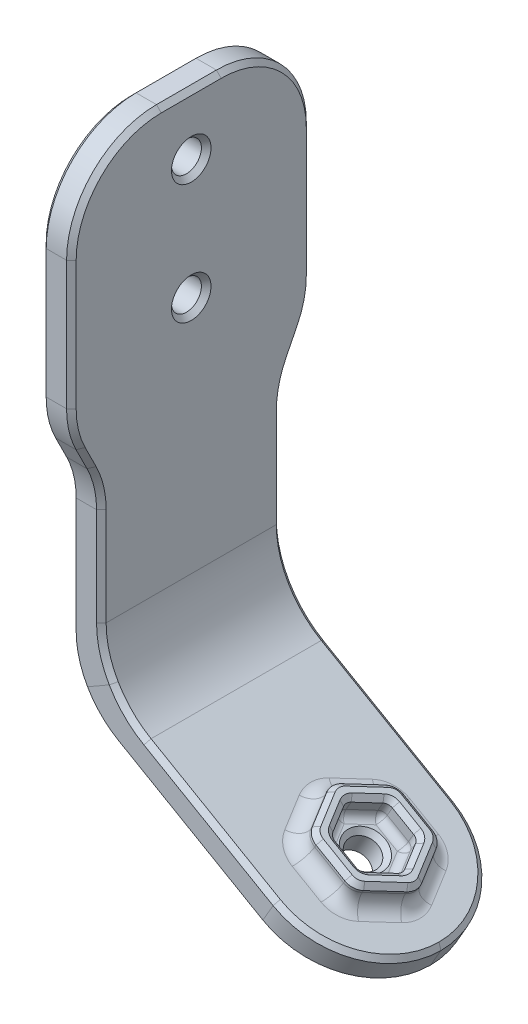
SolidWorks part; units mm, degrees
material "Onyx"
ref_plane "Front Plane" through (0, 0, 0) normal (0, 0, 1) x (1, 0, 0)
ref_plane "Top Plane" through (0, 0, 0) normal (0, 1, 0) x (1, 0, 0)
ref_plane "Right Plane" through (0, 0, 0) normal (1, 0, 0) x (0, 0, -1)
sketch "Sketch1" plane through (0, 0, 0) normal (0, 0, 1) x (1, 0, 0)
  line L0 (0, 0) -> (0, -31.75)
  line L1 (0, -31.75) -> (0, -50.8)
  line L2 (0, -50.8) -> (27.4963, -66.675)
  dimension "D2" = 19.05
  dimension "D1" = 31.75
  dimension "D3" = 180
  dimension "D4" = 120
  dimension "D5" = 31.75
sketch "Sketch2" plane through (0, 0, 0) normal (0, 1, 0) x (1, 0, 0)
  line L1 (-1.5875, -9.525) -> (1.5875, -9.525)
  line L2 (-1.5875, -9.525) -> (-1.5875, 9.525)
  line L3 (-1.5875, 9.525) -> (1.5875, 9.525)
  line L4 (1.5875, -9.525) -> (1.5875, 9.525)
  line L5 (-1.5875, -9.525) -> (1.5875, 9.525) construction
  line L6 (-1.5875, 9.525) -> (1.5875, -9.525) construction
  point P0 (0, 0)
  dimension "D1" = 3.175
  dimension "D2" = 19.05
sweep "Sweep1" add profiles "Sketch2" path "Sketch1"
sketch "Sketch4" plane through (-1.5875, 0, 0) normal (-1, 0, 0) x (0, 0, 1)
  line L0 (-12.7, -25.4) -> (-9.525, -31.75)
  line L1 (-12.7, 0) -> (12.7, 0)
  line L2 (-12.7, 0) -> (-12.7, -25.4)
  line L3 (-12.7, -25.4) -> (12.7, -25.4) construction
  line L4 (12.7, 0) -> (12.7, -25.4)
  line L5 (-9.525, 0) -> (-9.525, -31.75) construction
  line L6 (-9.525, -31.75) -> (9.525, -31.75)
  line L7 (9.525, 0) -> (9.525, -31.75) construction
  line L8 (9.525, -31.75) -> (12.7, -25.4)
  point P4 (0, 0)
  dimension "D1" = 25.4
  dimension "D2" = 6.35
  dimension "D3" = 25.4
extrude "Boss-Extrude1" add sketch "Sketch4" against normal up to surface (3.175 mm away) up to face at (1.5875, -15.875, 0)
sketch "Sketch3" plane through (-1.5875, 0, 0) normal (-1, 0, 0) x (0, 0, 1)
  line L0 (0, -19.05) -> (0, -6.35) construction
  line L1 (0, -6.35) -> (0, 0) construction
  circle A0 centre (0, -6.35) radius 1.5875
  circle A1 centre (0, -19.05) radius 1.5875
  dimension "D1" = 3.175
  dimension "D2" = 6.35
  dimension "D3" = 12.7
extrude "Cut-Extrude1" cut sketch "Sketch3" against normal up to next
sketch "Sketch5" plane through (-21.2033, -36.7252, 0) normal (0.5, 0.866, 0) x (0.866, -0.5, 0)
  line L0 (47.625, 0) -> (57.15, 0) construction
  line L1 (57.15, -9.525) -> (57.15, 9.525) construction
  circle A0 centre (47.625, 0) radius 1.5875
  dimension "D1" = 3.175
  dimension "D2" = 9.525
extrude "Cut-Extrude2" cut sketch "Sketch5" against normal up to next
sketch "Sketch6" plane through (-21.2033, -36.7252, 0) normal (0.5, 0.866, 0) x (0.866, -0.5, 0)
  line L1 (49.3848, 3.048) -> (45.8652, 3.048)
  line L2 (45.8652, 3.048) -> (44.1055, 0)
  line L3 (44.1055, 0) -> (45.8652, -3.048)
  line L4 (45.8652, -3.048) -> (49.3848, -3.048)
  line L5 (49.3848, -3.048) -> (51.1445, 0)
  line L6 (51.1445, 0) -> (49.3848, 3.048)
  line L7 (50.3013, 4.6355) -> (44.9487, 4.6355)
  line L8 (44.9487, 4.6355) -> (42.2724, 0)
  line L9 (42.2724, 0) -> (44.9487, -4.6355)
  line L10 (44.9487, -4.6355) -> (50.3013, -4.6355)
  line L11 (50.3013, -4.6355) -> (52.9776, 0)
  line L12 (52.9776, 0) -> (50.3013, 4.6355)
  circle A0 centre (47.625, 0) radius 3.048 construction
  circle A1 centre (47.625, 0) radius 4.6355 construction
  dimension "D1" = 6.096
  dimension "D2" = 1.5875
extrude "Boss-Extrude2" add sketch "Sketch6" along normal blind 2.3813
fillet "Fillet1" radius 9.525 2 edges at (27.4963, -66.675, -9.525) (27.4963, -66.675, 9.525)
fillet "Fillet2" radius 9.525 2 edges at (-1.5875, -51.7165, 0) (1.5875, -49.8835, 0)
fillet "Fillet3" radius 9.525 6 edges at (0, 0, -12.7) (0, 0, 12.7) (0, -25.4, -12.7) (0, -31.75, -9.525) (0, -25.4, 12.7) (0, -31.75, 9.525)
fillet "Fillet4" radius 1.5875 12 edges at (25.272, -62.1829, 0) (16.001, -56.8303, 0) (18.3187, -58.1684, -4.6355) (22.9542, -60.8447, -4.6355) (18.3187, -58.1684, 4.6355) (22.9542, -60.8447, 4.6355) (20.0412, -60.5377, -4.6355) (16.5645, -58.5305, -2.3177) (16.5645, -58.5305, 2.3178) (20.0412, -60.5377, 4.6355) (23.5178, -62.5449, -2.3178) (23.5178, -62.5449, 2.3177)
fillet "Fillet5" radius 0.7937 12 edges at (20.0412, -60.5377, 3.048) (17.7552, -59.2179, 1.524) (20.0412, -60.5377, -3.048) (22.3272, -61.8575, -1.524) (22.3272, -61.8575, 1.524) (17.7552, -59.2179, -1.524) (17.5885, -57.7468, 0) (19.1125, -58.6267, 3.048) (22.1605, -60.3865, 3.048) (23.6845, -61.2663, 0) (22.1605, -60.3865, -3.048) (19.1125, -58.6267, -3.048)
chamfer "Chamfer1" distance 0.508 angle 45 72 edges at (19.761, -57.6263, -2.9417) (18.9458, -57.1556, -1.524) (18.2901, -56.7771, 0) (18.9458, -57.1556, 1.524) (19.761, -57.6263, 2.9417) (21.2318, -58.4755, 3.048) (22.7026, -59.3246, 2.9417) (23.5178, -59.7953, 1.524) (24.1734, -60.1738, 0) (23.5178, -59.7953, -1.524) (22.7026, -59.3246, -2.9417) (21.2318, -58.4755, -3.048) (23.4432, -59.7522, 4.4228) (21.2318, -58.4755, 4.6355) (19.0204, -57.1987, 4.4228) (17.7552, -56.4682, 2.3178) (16.809, -55.9219, 0) (17.7552, -56.4682, -2.3177) (19.0204, -57.1987, -4.4228) (21.2318, -58.4755, -4.6355) (23.4432, -59.7522, -4.4228) (24.7084, -60.4827, -2.3178) (25.6546, -61.029, 0) (24.7084, -60.4827, 2.3177) (17.0788, -62.4936, 0) (18.6663, -59.7439, 0) (1.5875, -7.9375, 0) (-1.5875, -7.9375, 0) (1.5875, -20.6375, 0) (-1.5875, -20.6375, 0) (-1.5875, -28.575, -11.1125) (1.5875, -28.575, -11.1125) (1.5875, -31.8102, -9.7798) (1.5875, -25.3398, -12.4452) (1.5875, -39.1914, -9.525) (-1.5875, -16.3382, -12.7) (1.5875, -16.3382, -12.7) (1.9121, -46.8494, -9.525) (1.5875, -2.7898, -9.9102) (4.3773, -51.1194, -9.525) (1.5875, 0, 0) (13.1956, -56.5854, -9.525) (1.5875, -2.7898, 9.9102) (25.874, -63.9053, -6.7352) (1.5875, -16.3382, 12.7) (-1.5875, -16.3382, 12.7) (25.874, -63.9053, 6.7352) (1.5875, -25.3398, 12.4452) (13.1956, -56.5854, 9.525) (1.5875, -28.575, 11.1125) (-1.5875, -28.575, 11.1125) (4.3773, -51.1194, 9.525) (1.5875, -31.8102, 9.7798) (1.9121, -46.8494, 9.525) (1.5875, -39.1914, 9.525) (-1.5875, -31.8102, -9.7798) (-1.5875, -25.3398, -12.4452) (-1.5875, -40.1079, -9.525) (-1.2629, -48.6825, -9.525) (-1.5875, -2.7898, -9.9102) (1.2023, -52.9525, -9.525) (-1.5875, 0, 0) (10.8143, -58.8767, -9.525) (-1.5875, -2.7898, 9.9102) (24.2865, -66.6549, -6.7352) (24.2865, -66.6549, 6.7352) (-1.5875, -25.3398, 12.4452) (10.8143, -58.8767, 9.525) (1.2023, -52.9525, 9.525) (-1.5875, -31.8102, 9.7798) (-1.2629, -48.6825, 9.525) (-1.5875, -40.1079, 9.525)
